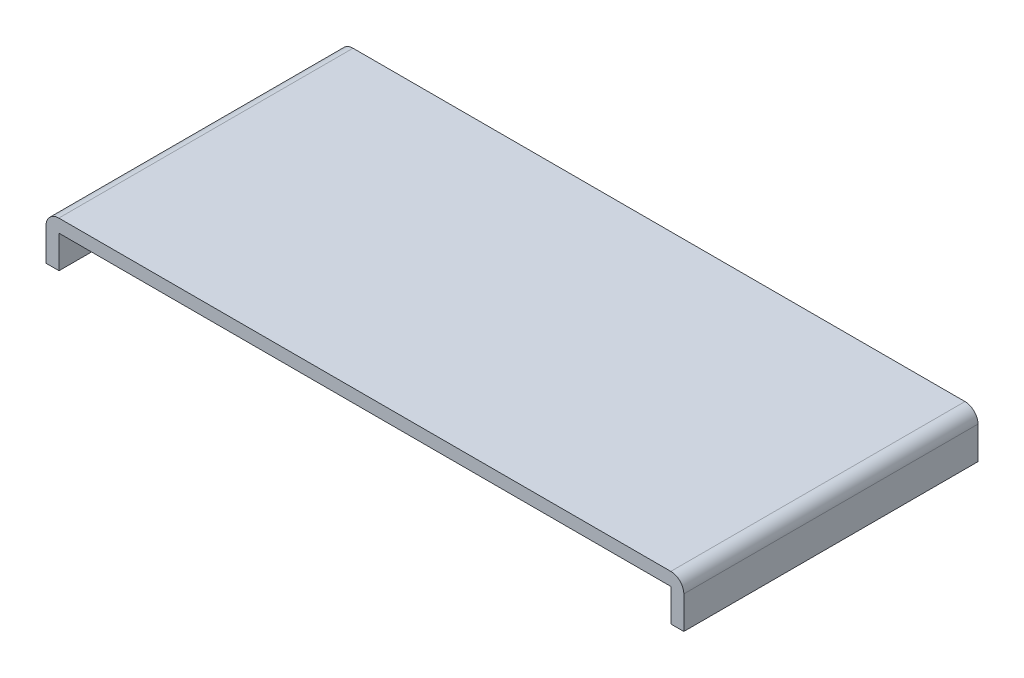
SolidWorks part; units mm, degrees
ref_plane "Front Plane" through (0, 0, 0) normal (0, 0, 1) x (1, 0, 0)
ref_plane "Top Plane" through (0, 0, 0) normal (0, 1, 0) x (1, 0, 0)
ref_plane "Right Plane" through (0, 0, 0) normal (1, 0, 0) x (0, 0, -1)
sketch "Sketch1" plane through (0, 0, 0) normal (0, 1, 0) x (1, 0, 0)
  line L1 (0, 0) -> (124.46, 0)
  line L2 (0, 0) -> (0, 57.404)
  line L3 (0, 57.404) -> (124.46, 57.404)
  line L4 (124.46, 0) -> (124.46, 57.404)
extrude "Boss-Extrude1" add sketch "Sketch1" along normal blind 2.54
sketch "Sketch2" plane through (0, 0, 0) normal (0, 0, 1) x (1, 0, 0)
  line L1 (0, 0) -> (124.46, 0) construction
  line L2 (4.572, 0) -> (0, 0)
  line L3 (0, 2.54) -> (124.46, 2.54) construction
  arc A0 (0, 0) -> (2.5043, 2.54) centre (2.5222, 0.0178) cw
extrude "Cut-Extrude1" cut sketch "Sketch2" against normal through all and the other way through all contours L2 A0
sketch "Sketch3" plane through (0, 0, 0) normal (0, 0, 1) x (1, 0, 0)
  line L0 (124.46, 0) -> (121.92, 0)
  line L1 (0, 0) -> (124.46, 0) construction
  line L2 (121.92, 0) -> (124.46, 0)
  line L3 (121.92, 0) -> (121.92, 2.54)
  line L4 (2.5043, 2.54) -> (124.46, 2.54) construction
  line L5 (121.92, 2.54) -> (121.92, 0)
sketch "Sketch4" plane through (0, 0, 0) normal (0, 0, 1) x (1, 0, 0)
  arc A0 (121.92, 2.54) -> (124.46, 0) centre (121.92, 0) cw
extrude "Cut-Extrude2" cut sketch "Sketch4" against normal through all and the other way through all contours A0
sketch "Sketch5" plane through (0, 0, 0) normal (0, -1, 0) x (1, 0, 0)
  line L0 (124.46, -57.404) -> (0, -57.404) construction
  line L1 (0, 0) -> (2.54, 0)
  line L2 (0, 0) -> (0, -57.404)
  line L3 (0, -57.404) -> (2.54, -57.404)
  line L4 (2.54, 0) -> (2.54, -57.404)
extrude "Boss-Extrude2" add sketch "Sketch5" along normal blind 6.35
sketch "Sketch7" plane through (0, 0, 0) normal (0, -1, 0) x (1, 0, 0)
  line L0 (124.46, -57.404) -> (2.54, -57.404) construction
  line L1 (124.46, 0) -> (121.92, 0)
  line L2 (124.46, 0) -> (124.46, -57.404)
  line L3 (124.46, -57.404) -> (121.92, -57.404)
  line L4 (121.92, 0) -> (121.92, -57.404)
extrude "Boss-Extrude3" add sketch "Sketch7" along normal blind 6.35
